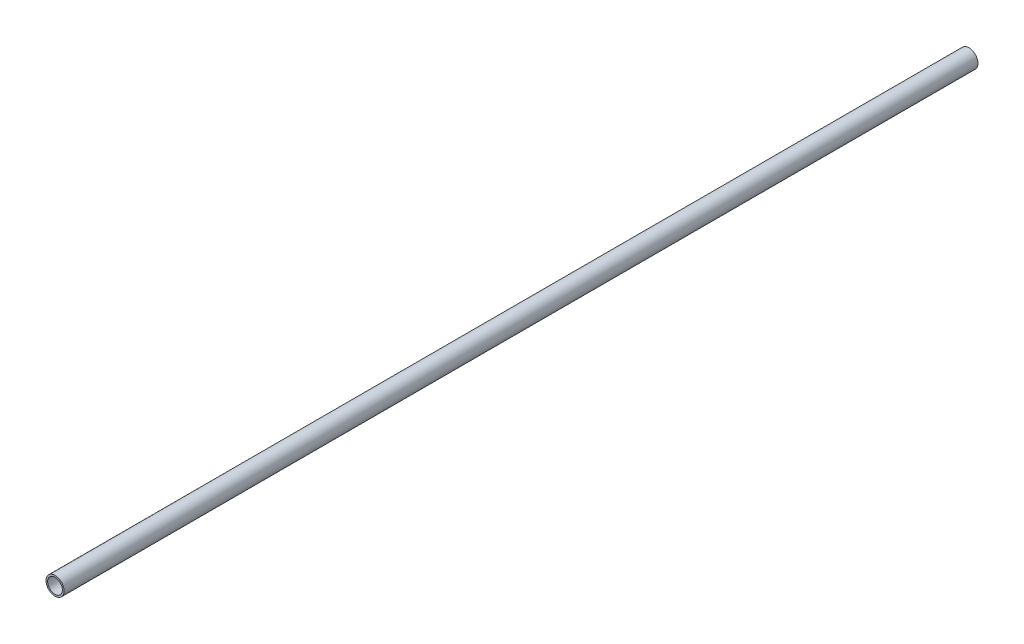
SolidWorks part; units mm, degrees
ref_plane "Front Plane" through (0, 0, 0) normal (0, 0, 1) x (1, 0, 0)
ref_plane "Top Plane" through (0, 0, 0) normal (0, 1, 0) x (1, 0, 0)
ref_plane "Right Plane" through (0, 0, 0) normal (1, 0, 0) x (0, 0, -1)
sketch "Sketch1" plane through (0, 0, 0) normal (0, 0, 1) x (1, 0, 0)
  circle A0 centre (0, 0) radius 30.1625
  dimension "Pipe OD" = 60.325
extrude "Extrude-Thin1" add sketch "Sketch1" along normal mid plane 3048 thin thin type one direction reverse wall 5.5372
